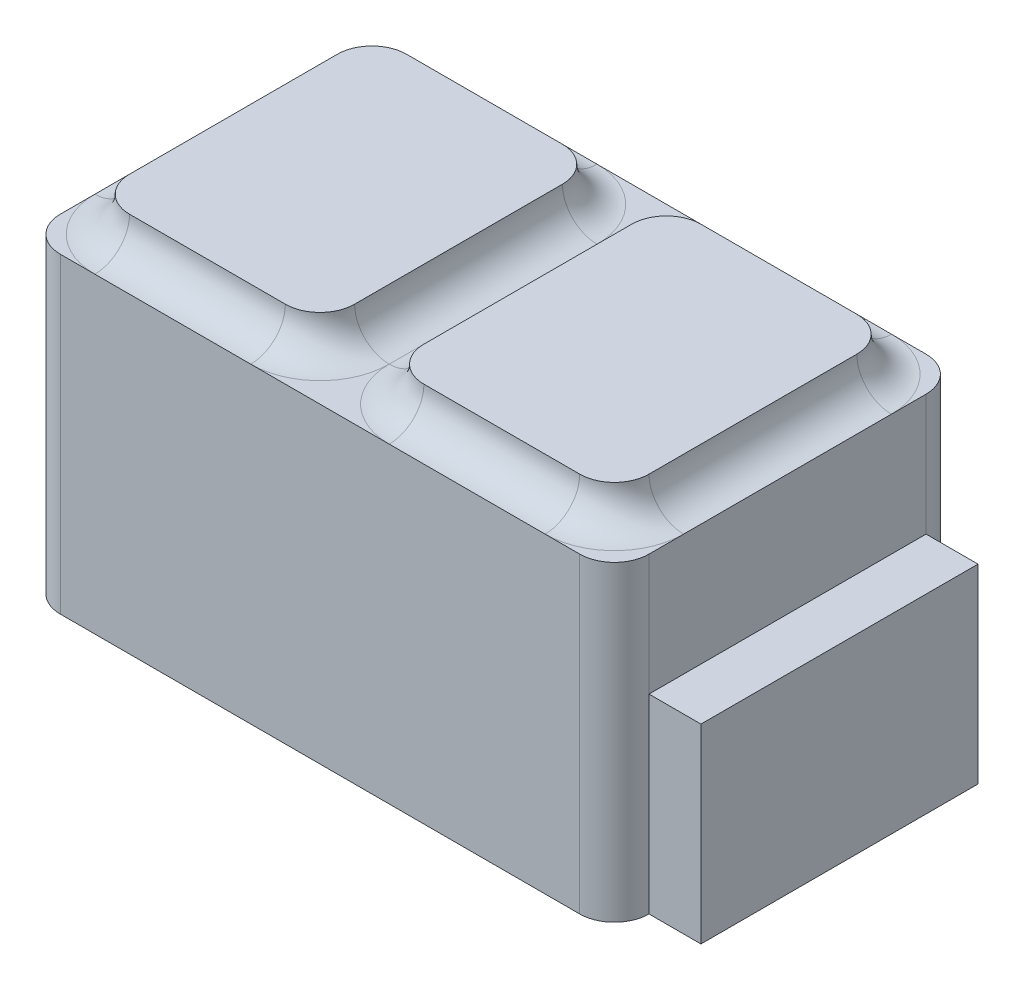
SolidWorks part; units mm, degrees
ref_plane "Front Plane" through (0, 0, 0) normal (0, 0, 1) x (1, 0, 0)
ref_plane "Top Plane" through (0, 0, 0) normal (0, 1, 0) x (1, 0, 0)
ref_plane "Right Plane" through (0, 0, 0) normal (1, 0, 0) x (0, 0, -1)
sketch "Sketch1" plane through (0, 0, 0) normal (0, 1, 0) x (1, 0, 0)
  line L1 (-7.5, -5) -> (7.5, -5)
  line L2 (-8.5, -4) -> (-8.5, 4)
  line L3 (-7.5, 5) -> (7.5, 5)
  line L4 (8.5, -4) -> (8.5, 4)
  line L5 (-8.5, -5) -> (8.5, 5) construction
  line L6 (-8.5, 5) -> (8.5, -5) construction
  arc A0 (7.5, 5) -> (8.5, 4) centre (7.5, 4) cw
  arc A1 (7.5, -5) -> (8.5, -4) centre (7.5, -4) ccw
  arc A2 (-7.5, -5) -> (-8.5, -4) centre (-7.5, -4) cw
  arc A3 (-8.5, 4) -> (-7.5, 5) centre (-7.5, 4) cw
  point P0 (0, 0)
  dimension "D3" = 1
  dimension "D1" = 10
  dimension "D2" = 17
extrude "Boss-Extrude1" add sketch "Sketch1" along normal blind 10
sketch "Sketch2" plane through (0, 0, 0) normal (0, 1, 0) x (1, 0, 0)
  line L1 (-7, -3.5) -> (7, -3.5)
  line L2 (-7, -3.5) -> (-7, 3.5)
  line L3 (-7, 3.5) -> (7, 3.5)
  line L4 (7, -3.5) -> (7, 3.5)
  line L5 (-7, -3.5) -> (7, 3.5) construction
  line L6 (-7, 3.5) -> (7, -3.5) construction
  circle A0 centre (0, 0) radius 1.75
  point P0 (0, 0)
  dimension "D3" = 3.5
  dimension "D1" = 1.5
  dimension "D2" = 1.5
extrude "Cut-Extrude1" cut sketch "Sketch2" along normal blind 8
sketch "Sketch3" plane through (-7, 0, 0) normal (1, 0, 0) x (0, 0, -1)
  line L0 (3.5, 0) -> (-3.5, 0) construction
  line L1 (-0.5, 2) -> (0.5, 2)
  line L2 (-0.5, 2) -> (-0.5, 0)
  line L3 (-0.5, 0) -> (0.5, 0)
  line L4 (0.5, 2) -> (0.5, 0)
  line L5 (-0.5, 2) -> (0.5, 0) construction
  line L6 (-0.5, 0) -> (0.5, 2) construction
  point P0 (0, 1)
  point P7 (0, 0)
  point P8 (0, 0)
  dimension "D1" = 2
  dimension "D2" = 1
extrude "Boss-Extrude2" add sketch "Sketch3" along normal blind 14
sketch "Sketch4" plane through (0, 0, 0) normal (0, -1, 0) x (1, 0, 0)
  line L4 (8.5, -4) -> (10, -4)
  line L5 (10, -4) -> (10, 4)
  line L6 (10, 4) -> (8.5, 4)
  line L9 (8.5, -4) -> (8.5, 4)
  dimension "D2" = 1.5
extrude "Boss-Extrude3" add sketch "Sketch4" against normal blind 5.5
sketch "Sketch5" plane through (0, 10, 0) normal (0, 1, 0) x (1, 0, 0)
  line L0 (7.5, 5) -> (-7.5, 5) construction
  line L1 (-1, -4) -> (-7.5, -4)
  line L2 (-1, -4) -> (-1, 4)
  line L3 (-1, 4) -> (-7.5, 4)
  line L4 (-7.5, -4) -> (-7.5, 4)
  line L5 (-1, -4) -> (-7.5, 4) construction
  line L6 (-1, 4) -> (-7.5, -4) construction
  line L7 (7.5, -4) -> (1, -4)
  line L8 (7.5, -4) -> (7.5, 4)
  line L9 (7.5, 4) -> (1, 4)
  line L10 (1, -4) -> (1, 4)
  line L11 (7.5, -4) -> (1, 4) construction
  line L12 (7.5, 4) -> (1, -4) construction
  line L13 (-8.5, -5) -> (8.5, -5)
  line L14 (-8.5, -5) -> (-8.5, 5)
  line L15 (-8.5, 5) -> (8.5, 5)
  line L16 (8.5, -5) -> (8.5, 5)
  line L17 (-8.5, -5) -> (8.5, 5) construction
  line L18 (-8.5, 5) -> (8.5, -5) construction
  line L19 (-8.5, 4) -> (-8.5, -4) construction
  point P0 (-4.25, 0)
  point P5 (4.25, 0)
  point P13 (0, 0)
  dimension "D1" = 1
  dimension "D2" = 1
  dimension "D3" = 1
  dimension "D4" = 2
extrude "Cut-Extrude2" cut sketch "Sketch5" against normal blind 1
fillet "Fillet2" radius 1 8 edges at (4.25, 9, 4) (7.5, 9, 0) (4.25, 9, -4) (-4.25, 9, -4) (-7.5, 9, 0) (-4.25, 9, 4) (1, 9, 0) (-1, 9, 0)
